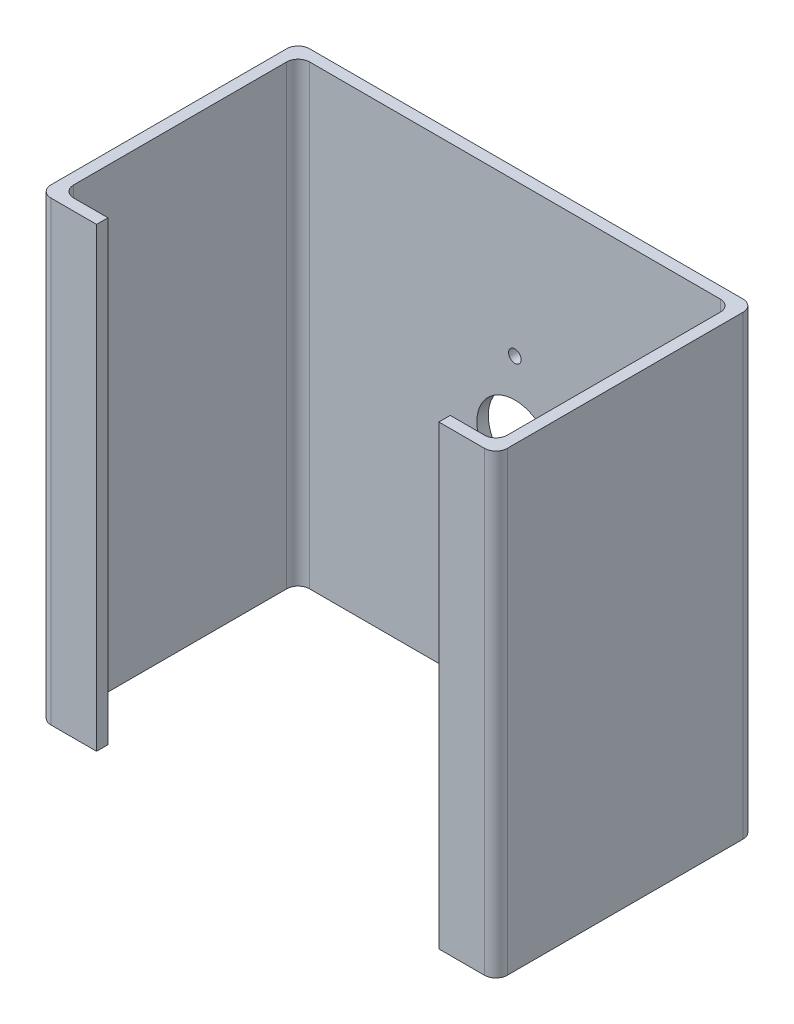
SolidWorks part; units mm, degrees
ref_plane "前视基准面" through (0, 0, 0) normal (0, 0, 1) x (1, 0, 0)
ref_plane "上视基准面" through (0, 0, 0) normal (0, 1, 0) x (1, 0, 0)
ref_plane "右视基准面" through (0, 0, 0) normal (1, 0, 0) x (0, 0, -1)
sketch "草图1" plane through (0, 0, 0) normal (0, 1, 0) x (1, 0, 0)
  line L0 (0, 0) -> (-12, 0)
  line L1 (-12, 0) -> (-12, 62)
  line L2 (-12, 62) -> (102, 62)
  line L3 (102, 62) -> (102, 0)
  line L4 (102, 0) -> (90, 0)
  line L5 (90, 0) -> (90, -3)
  line L6 (90, -3) -> (105, -3)
  line L7 (105, -3) -> (105, 65)
  line L8 (105, 65) -> (-15, 65)
  line L9 (-15, 65) -> (-15, -3)
  line L10 (-15, -3) -> (0, -3)
  line L11 (0, -3) -> (0, 0)
  dimension "D1" = 15
  dimension "D2" = 15
  dimension "D3" = 120
  dimension "D4" = 68
  dimension "D5" = 3
  dimension "D6" = 3
  dimension "D7" = 3
  dimension "D8" = 3
  dimension "D9" = 3
  dimension "D10" = 68
base flange "基体-法兰1" sketch "草图1" thickness 120 reverse thickness direction no parameters "D1"=0.7366
sketch "草图6" plane through (0, 0, -65) normal (0, 0, -1) x (-1, 0, 0)
  line L0 (-45, -60) -> (-45, -40) construction
  line L1 (-45, -60) -> (-27.6795, -70) construction
  line L2 (-45, -60) -> (-62.3205, -70) construction
  circle A0 centre (-45, -60) radius 10
  circle A1 centre (-45, -60) radius 20 construction
  circle A2 centre (-62.3205, -70) radius 1.65
  circle A3 centre (-45, -40) radius 1.65
  circle A4 centre (-27.6795, -70) radius 1.65
  dimension "D1" = 40
  dimension "D2" = 20
  dimension "D5" = 3.3
  dimension "D6" = 3.3
  dimension "D7" = 3.3
  dimension "D3" = 120
  dimension "D4" = 120
extrude "切除-拉伸1" cut sketch "草图6" against normal blind 10 normal cut yes
fillet "圆角1" radius 3 8 edges at (105, -60, 3) (102, -60, 0) (-12, -60, 0) (-15, -60, 3) (102, -60, -62) (-12, -60, -62) (105, -60, -65) (-15, -60, -65)
sketch "折弯-线1" plane through (0, 0, 0) normal (0, 1, 0) x (1, 0, 0)
sketch "边界框1" plane through (0, 0, 0) normal (0, 1, 0) x (1, 0, 0)
sheet metal parameters "钣金6" thickness 120 parameters "D1"=0.7366
flat pattern "平板型式6" [suppressed]
sketch "折弯-线2" plane through (0, 0, 0) normal (0, 1, 0) x (1, 0, 0)
sketch "边界框2" [suppressed] plane through (0, 0, 0) normal (0, 1, 0) x (1, 0, 0)
sheet metal parameters "钣金7" thickness 120 parameters "D1"=0.7366
flat pattern "平板型式6"
sketch "折弯-线2" plane through (0, 0, 0) normal (0, 1, 0) x (1, 0, 0)
sketch "边界框2" [suppressed] plane through (0, 0, 0) normal (0, 1, 0) x (1, 0, 0)
